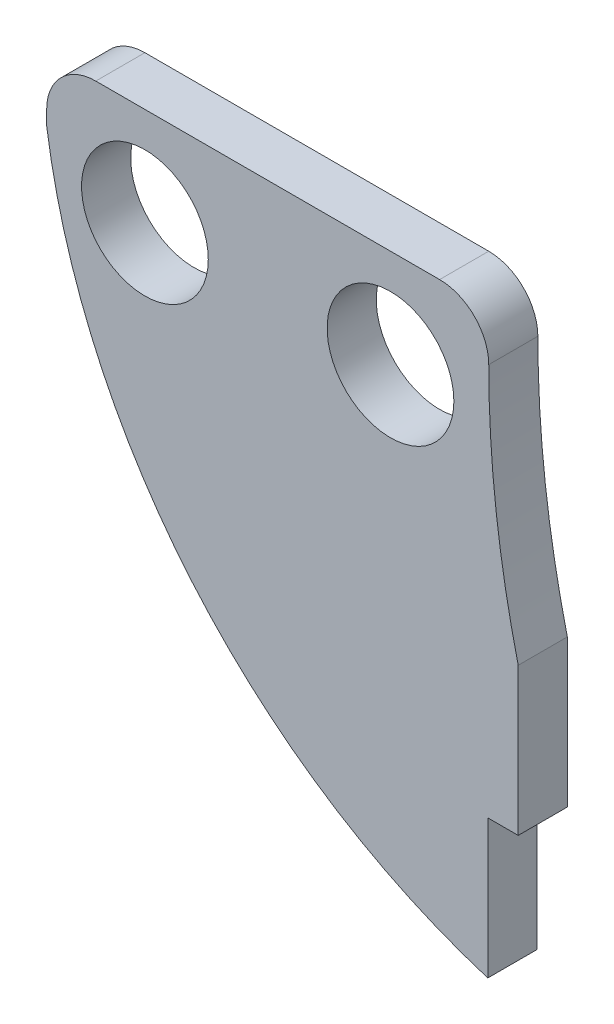
SolidWorks part; units mm, degrees
material "Teak"
ref_plane "Front Plane" through (0, 0, 0) normal (0, 0, 1) x (1, 0, 0)
ref_plane "Top Plane" through (0, 0, 0) normal (0, 1, 0) x (1, 0, 0)
ref_plane "Right Plane" through (0, 0, 0) normal (1, 0, 0) x (0, 0, -1)
sketch "Sketch2" plane through (0, 0, 0) normal (0, 0, 1) x (1, 0, 0)
  line L0 (0, 0) -> (0, -14.2941) construction
  line L1 (22.6507, -27.1834) -> (22.6507, -57.1834)
  line L2 (-25.3493, -3.6334) -> (-25.3493, 2.8166)
  line L3 (-25.3493, 2.8166) -> (19.6507, 2.8166)
  line L4 (19.6507, -2.1834) -> (19.6507, 2.8166)
  line L5 (-25.3493, -3.6334) -> (19.6507, 2.8166) construction
  line L6 (-25.3493, 2.8166) -> (19.6507, -2.1834) construction
  circle A0 centre (9.6507, -7.1834) radius 6.45
  circle A1 centre (-15.3493, -7.1834) radius 6.45
  arc A2 (19.6507, -2.1834) -> (22.6507, -27.1834) centre (125.3173, -2.1834) ccw
  arc A3 (-25.3493, -3.6334) -> (22.6507, -57.1834) centre (38.7755, 5.5578) ccw
  point P0 (0, 0)
  dimension "D1" = 12.9
  dimension "D5" = 12.9
  dimension "D9" = 30
  dimension "D10" = 10
  dimension "D2" = 6.45
  dimension "D12" = 25
  dimension "D3" = 10
  dimension "D4" = 10
  dimension "D6" = 25
  dimension "D7" = 50
  dimension "D8" = 13
  dimension "D11" = 0
extrude "Boss-Extrude1" add sketch "Sketch2" along normal blind 5
sketch "Sketch3" plane through (0, 0, 0) normal (0, 1, 0) x (1, 0, 0)
  line L0 (22.6507, -5) -> (22.6507, 0)
  line L1 (22.6507, -5) -> (19.5507, -5)
  line L2 (22.6507, 0) -> (19.5507, 0)
  line L3 (19.5507, -5) -> (19.5507, 0)
  dimension "D1" = 3.1
extrude "Cut-Extrude1" cut sketch "Sketch3" along normal blind 15 from vertex starting at point (22.6507, -57.1834, 5)
fillet "Fillet1" radius 5 2 edges at (-25.3493, 2.8166, 2.5) (19.6507, 2.8166, 2.5)
equation "\"D4@Sketch2\"=\"D3@Sketch2\""
equation "\"p\"= 20mm"
equation "\"m\"= 1"
equation "\"hole_diam\"= 4mm"
equation "\"D1@Sketch2\"=\"small_bearing_outer\"-.1"
equation "\"D5@Sketch2\"=\"D1@Sketch2\""
equation "\"D6@Sketch2\"=25"
equation "\"D7@Sketch2\"=\"len_grip_2\""
equation "\"len_grip_1\" = 50mm"
equation "\"len_grip_2\" = 50mm"
equation "\"thick\" = 3.1mm"
equation "\"thick2\" = 20mm"
equation "\"wrist_cont_bearing_diam\"=3in"
equation "\"wrist_cont_bearing_thick\"=5/16in"
equation "\"len_forearm\" = 300mm"
equation "\"wrist_bearing_diam\"=3in"
equation "\"len_link\" = 7cm"
equation "\"elbow_cont_bearing_diam\"=10cm"
equation "\"elbow_cont_bearing2_diam\"=7.5cm"
equation "\"small_bearing_outer\"=13mm"
equation "\"servo1_L\"=40.7mm"
equation "\"servo1_W\"=20.5mm"
equation "\"servo1_H\"=43.5mm"
equation "\"servo1_hL\"=49mm"
equation "\"servo1_hW\"=10mm"
equation "\"D10@Sketch2\"=\"D3@Sketch2\""
equation "\"D8@Sketch2\"=\"small_bearing_outer\""
equation "\"D2@Sketch2\"=\"D1@Sketch2\"/2"
equation "\"D1@Sketch3\"=\"thick\""
